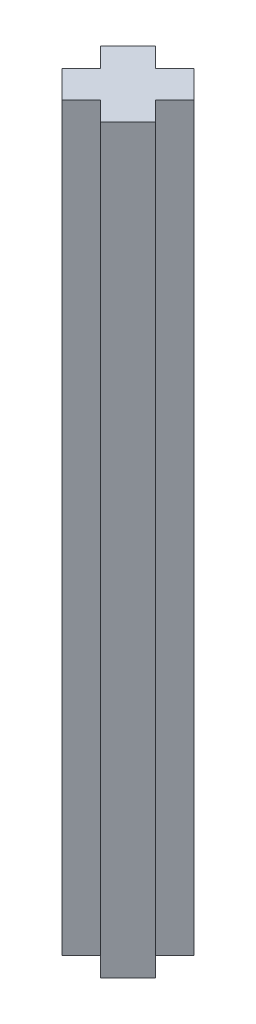
SolidWorks part; units mm, degrees
ref_plane "Front Plane" through (0, 0, 0) normal (0, 0, 1) x (1, 0, 0)
ref_plane "Top Plane" through (0, 0, 0) normal (0, 1, 0) x (1, 0, 0)
ref_plane "Right Plane" through (0, 0, 0) normal (1, 0, 0) x (0, 0, -1)
sketch "Sketch1" plane through (0, 0, 0) normal (0, 1, 0) x (1, 0, 0)
  line L0 (-0.627, 2.9162) -> (-2.423, 4.7122)
  line L1 (-3.167, -2.1638) -> (1.913, -2.1638) construction
  line L2 (-3.167, -2.1638) -> (-3.167, 2.9162) construction
  line L3 (-3.167, 2.9162) -> (1.913, 2.9162) construction
  line L4 (1.913, -2.1638) -> (1.913, 2.9162) construction
  line L5 (-3.167, -2.1638) -> (1.913, 2.9162) construction
  line L6 (-3.167, 2.9162) -> (1.913, -2.1638) construction
  line L7 (-3.167, 0.3762) -> (-4.963, 2.1722)
  line L8 (-4.963, 2.1722) -> (-2.423, 4.7122)
  line L9 (1.913, 0.3762) -> (3.7091, -1.4199)
  line L10 (-0.627, -2.1638) -> (1.1691, -3.9599)
  line L11 (1.1691, -3.9599) -> (3.7091, -1.4199)
  line L12 (-3.167, 0.3762) -> (-4.963, -1.4199)
  line L13 (-0.627, -2.1638) -> (-2.423, -3.9599)
  line L14 (-4.963, -1.4199) -> (-2.423, -3.9599)
  line L15 (1.913, 0.3762) -> (3.7091, 2.1722)
  line L16 (1.1691, 4.7122) -> (3.7091, 2.1722)
  line L17 (-0.627, 2.9162) -> (1.1691, 4.7122)
  point P0 (-0.627, 0.3762)
  dimension "D1" = 2.54
  dimension "D2" = 5.08
  dimension "D3" = 5.08
  dimension "D4" = 8.6721
  dimension "D5" = 3.5921
  dimension "D6" = 3.5921
  dimension "D7" = 3.5921
  dimension "D8" = 3.5921
  dimension "D9" = 8.6721
  dimension "D10" = 0
  dimension "D11" = 3.5921
  dimension "D12" = 5.08
  dimension "D13" = 2.54
  dimension "D14" = 2.54
  dimension "D15" = 2.54
  dimension "D16" = 2.54
  dimension "D17" = 2.54
  dimension "D18" = 2.54
  dimension "D19" = 2.54
  dimension "D20" = 2.54
extrude "Boss-Extrude1" add sketch "Sketch1" along normal blind 69.0217
scale "Scale1" scale about centroid uniform scaling yes scale factor 0.92
